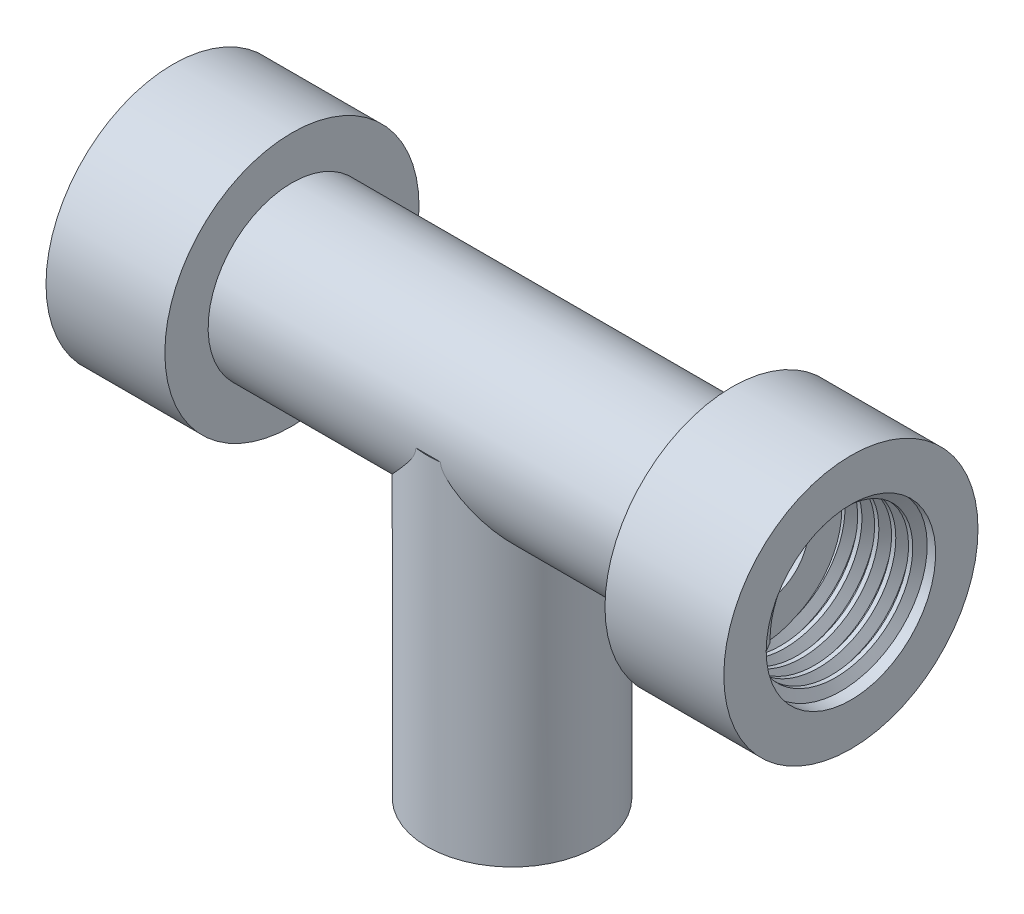
SolidWorks part; units mm, degrees
ref_plane "Front Plane" through (0, 0, 0) normal (0, 0, 1) x (1, 0, 0)
ref_plane "Top Plane" through (0, 0, 0) normal (0, 1, 0) x (1, 0, 0)
ref_plane "Right Plane" through (0, 0, 0) normal (1, 0, 0) x (0, 0, -1)
sketch "Sketch4" plane through (0, 0, 0) normal (0, 0, 1) x (1, 0, 0)
  line L0 (0, 0) -> (0, -25.4)
  line L1 (0, -25.4) -> (6.35, -25.4)
  line L2 (6.35, -25.4) -> (6.35, 0)
  line L3 (6.35, 0) -> (0, 0)
  dimension "D1" = 25.4
  dimension "D2" = 6.35
revolve "Revolve2" add sketch "Sketch4" angle 360 about L0
sketch "Sketch5" plane through (0, 0, 0) normal (0, 0, 1) x (1, 0, 0)
  line L0 (0, 0) -> (0, -6.35)
  line L1 (0, -6.35) -> (-0.0171, -6.2817)
  line L2 (-0.0171, -6.2817) -> (16.4929, -6.2817)
  line L3 (16.4929, -6.2817) -> (16.4929, -9.525)
  line L4 (16.4929, -9.525) -> (25.4, -9.525)
  line L5 (25.4, -9.525) -> (25.4, -6.35)
  line L6 (25.4, -6.35) -> (19.05, -6.35)
  line L7 (19.05, -6.35) -> (19.05, 0)
  line L8 (19.05, 0) -> (0, 0)
  point P7 (0, 0)
  dimension "D1" = 6.35
  dimension "D2" = 19.05
  dimension "D3" = 16.51
  dimension "D4" = 6.35
  dimension "D5" = 3.175
  dimension "D6" = 6.35
  dimension "D7" = 90
revolve "Revolve5" add sketch "Sketch5" angle 360 about L8 region at (11.7154, -4.0604, 0)
mirror "Mirror1" about plane through (0, 0, 0) normal (1, 0, 0) of "Revolve5"
sketch "Sketch6" plane through (0, -25.4, 0) normal (0, -1, 0) x (-1, 0, 0)
  circle A0 centre (0, 0) radius 3.175
  dimension "D1" = 6.35
extrude "Cut-Extrude1" cut sketch "Sketch6" against normal blind 25.4
sketch "Sketch7" plane through (-19.05, 0, 0) normal (-1, 0, 0) x (0, 0, 1)
  circle A0 centre (0, 0) radius 3.175
extrude "Cut-Extrude2" cut sketch "Sketch7" against normal blind 38.1
thread "Thread2" pitch 1.27 method extrude profile "Thread Profile4" start angle 0, offset 0, length 0, pitch 1.27, diameter 12.7
ref_plane "Plane4" through (25.4, 0, 6.35) normal (0, -1, 0) x (0, 0, 1)
sketch "Thread Profile4" plane through (25.4, 0, 6.35) normal (0, -1, 0) x (0, 0, 1)
  line L0 (0, 0) -> (0, 1.27) construction
  line L11 (0, 0) -> (0, 1.1112)
  line L12 (0, 1.1112) -> (-0.6874, 0.7144)
  line L13 (-0.6874, 0.7144) -> (-0.6874, 0.3969)
  line L15 (-0.6874, 0.3969) -> (0, 0)
  line L17 (-0.6874, 0.5556) -> (0, 0.5556) construction
  point P2 (0, 0)
  dimension "Pitch" = 1.27
  dimension "Profile_Angle" = 60
  dimension "Profile_Land" = 0.3175
  dimension "Profile_Height" = 0.6874
thread "Thread3" pitch 1.27 method extrude profile "Thread Profile5" start angle 0, offset 0, length 0, pitch 1.27, diameter 12.7
ref_plane "Plane5" through (-19.05, 0, 6.35) normal (0, -1, 0) x (0, 0, 1)
sketch "Thread Profile5" plane through (-19.05, 0, 6.35) normal (0, -1, 0) x (0, 0, 1)
  line L0 (0, 0) -> (0, 1.27) construction
  line L11 (0, 0) -> (0, 1.1112)
  line L12 (0, 1.1112) -> (-0.6874, 0.7144)
  line L13 (-0.6874, 0.7144) -> (-0.6874, 0.3969)
  line L15 (-0.6874, 0.3969) -> (0, 0)
  line L17 (-0.6874, 0.5556) -> (0, 0.5556) construction
  point P2 (0, 0)
  dimension "Pitch" = 1.27
  dimension "Profile_Angle" = 60
  dimension "Profile_Land" = 0.3175
  dimension "Profile_Height" = 0.6874
